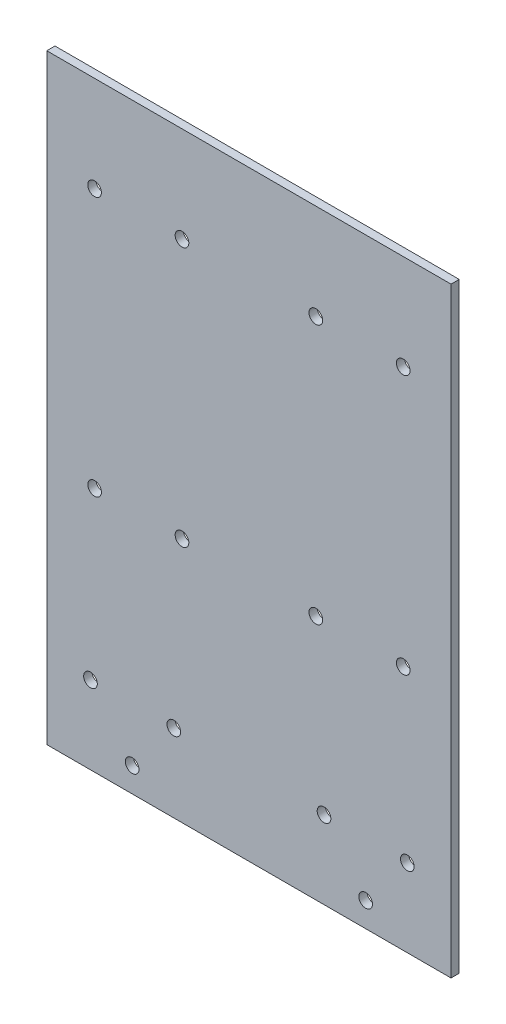
SolidWorks part; units mm, degrees
ref_plane "前视基准面" through (0, 0, 0) normal (0, 0, 1) x (1, 0, 0)
ref_plane "上视基准面" through (0, 0, 0) normal (0, 1, 0) x (1, 0, 0)
ref_plane "右视基准面" through (0, 0, 0) normal (1, 0, 0) x (0, 0, -1)
sketch "草图1" plane through (0, 0, 0) normal (0, 0, 1) x (1, 0, 0)
  line L0 (0, -110) -> (0, 110) construction
  line L1 (74, -110) -> (-74, -110)
  line L2 (74, -110) -> (74, 110)
  line L3 (74, 110) -> (-74, 110)
  line L4 (-74, -110) -> (-74, 110)
  line L5 (74, -110) -> (-74, 110) construction
  line L6 (74, 110) -> (-74, -110) construction
  circle A0 centre (-58, -81.5) radius 2.5
  circle A1 centre (-27.5, -81.5) radius 2.5
  circle A2 centre (-42.75, -101) radius 2.5
  circle A3 centre (42.75, -101) radius 2.5
  circle A4 centre (58, -81.5) radius 2.5
  circle A5 centre (27.5, -81.5) radius 2.5
  point P0 (0, 0)
  dimension "D3" = 5
  dimension "D4" = 5
  dimension "D5" = 5
  dimension "D6" = 9
  dimension "D7" = 16
  dimension "D8" = 30.5
  dimension "D9" = 19.5
  dimension "D10" = 15.25
  dimension "D1" = 148
  dimension "D2" = 220
extrude "凸台-拉伸1" add sketch "草图1" along normal blind 3
sketch "草图2" plane through (0, 0, 3) normal (0, 0, 1) x (1, 0, 0)
  line L0 (-74, 110) -> (-74, -110) construction
  line L1 (-74, -110) -> (74, -110) construction
  line L2 (0, 110) -> (0, -110) construction
  line L3 (74, 110) -> (-74, 110) construction
  circle A0 centre (-56.5, -20) radius 2.5
  circle A1 centre (-24.5, -20) radius 2.5
  circle A2 centre (-56.5, 75) radius 2.5
  circle A3 centre (-24.5, 75) radius 2.5
  circle A4 centre (-56.5, 170) radius 2.5
  circle A5 centre (-24.5, 170) radius 2.5
  circle A6 centre (24.5, 170) radius 2.5
  circle A7 centre (56.5, 170) radius 2.5
  circle A8 centre (24.5, 75) radius 2.5
  circle A9 centre (56.5, 75) radius 2.5
  circle A10 centre (24.5, -20) radius 2.5
  circle A11 centre (56.5, -20) radius 2.5
  dimension "D1" = 5
  dimension "D2" = 5
  dimension "D3" = 32
  dimension "D4" = 17.5
  dimension "D5" = 90
  dimension "D7" = 90
  dimension "D6" = 3
extrude "切除-拉伸1" cut sketch "草图2" against normal blind 3
